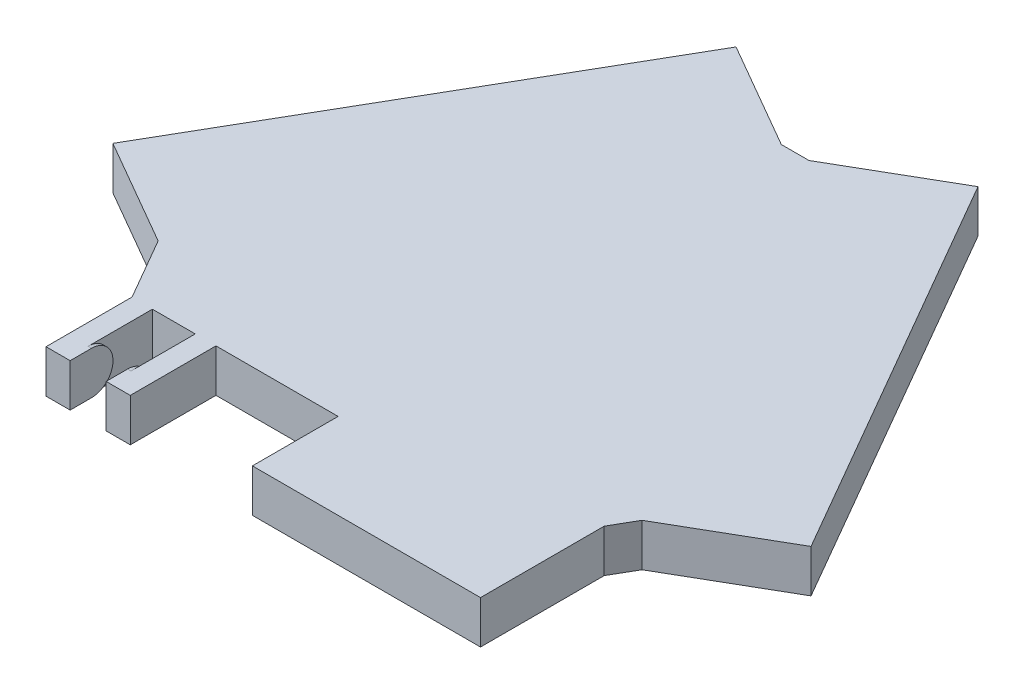
SolidWorks part; units mm, degrees
material "ABS"
ref_plane "Front Plane" through (0, 0, 0) normal (0, 0, 1) x (1, 0, 0)
ref_plane "Top Plane" through (0, 0, 0) normal (0, 1, 0) x (1, 0, 0)
ref_plane "Right Plane" through (0, 0, 0) normal (1, 0, 0) x (0, 0, -1)
sketch "Sketch1" plane through (0, 0, 0) normal (0, 1, 0) x (1, 0, 0)
  line L0 (23.6714, -35) -> (-23.6714, -35) construction
  line L1 (-21.9393, 38) -> (-43.8786, 0)
  line L2 (-33.8786, -17.3205) -> (-31.9393, -20.6795)
  line L3 (-21.9393, -38) -> (21.9393, -38)
  line L4 (-16.9393, 46.6603) -> (-1.9393, 38)
  line L5 (43.8786, 0) -> (21.9393, 38)
  line L6 (1.9393, 38) -> (-1.9393, 38)
  line L7 (-21.9393, -38) -> (-31.9393, -38)
  line L8 (-31.9393, -38) -> (-31.9393, -20.6795)
  line L9 (0, 0) -> (0, -38) construction
  line L10 (21.9393, -38) -> (31.9393, -38)
  line L11 (31.9393, -38) -> (31.9393, -20.6795)
  line L12 (31.9393, -20.6795) -> (33.8786, -17.3205)
  line L13 (21.9393, -38) -> (23.6714, -35) [skipped]
  line L14 (-21.9393, 38) -> (-16.9393, 46.6603)
  line L15 (-43.8786, 0) -> (-48.8786, -8.6603)
  line L16 (-48.8786, -8.6603) -> (-33.8786, -17.3205)
  line L17 (48.8786, -8.6603) -> (33.8786, -17.3205)
  line L18 (43.8786, 0) -> (48.8786, -8.6603)
  line L19 (21.9393, 38) -> (16.9393, 46.6603)
  line L20 (16.9393, 46.6603) -> (1.9393, 38)
  circle A1 centre (0, 0) radius 38 construction
  point P33 (0, 0)
  dimension "D1" = 35
  dimension "D2" = 76
  dimension "D3" = 3
  dimension "D4" = 10
  dimension "D5" = 43.8786
  dimension "D6" = 3
extrude "Boss-Extrude1" add sketch "Sketch1" along normal blind 6 contours L19 L20 L6 L4 L14 L1 L15 L16 L2 L8 L7 L3 L10 L11 L12 L17 L18 L5 region at (0, 0, 0)
sketch "Sketch2" plane through (0, 6, 0) normal (0, 1, 0) x (1, 0, 0)
  line L0 (-20, -40.1141) -> (-20, -26)
  line L1 (-20, -26) -> (-26, -26)
  line L2 (-17.1, -26) -> (0, -26)
  line L3 (-17.1, -40.1141) -> (0, -40.1141)
  line L4 (-20, -40.1141) -> (-17.1, -40.1141) construction
  line L5 (31.9393, -38) -> (-31.9393, -38) construction
  line L12 (-31.9393, -38) -> (-31.9393, -20.6795) construction
  line L13 (0, -26) -> (0, -40.1141)
  line L16 (-26, -26) -> (-26, -40.1141)
  line L17 (-26, -40.1141) -> (-28.9, -40.1141) construction
  line L18 (-17.1, -40.1141) -> (-17.1, -26)
  line L19 (-28.9, -40.1141) -> (-28.9, -25.9437)
  line L20 (-28.9, -25.9437) -> (-31.9393, -20.6795)
  line L21 (-31.9393, -20.6795) -> (-31.9393, -40.1141)
  line L22 (-31.9393, -40.1141) -> (-28.9, -40.1141)
  line L23 (-26, -40.1141) -> (-20, -40.1141)
  line L24 (0, 0) -> (0, -40.1141) construction
  line L25 (-20, -40.1141) -> (-20, -38)
  point P41 (0, 0)
  dimension "D2" = 12
  dimension "D3" = 20
  dimension "D5" = 6
  dimension "D4" = 2.9
extrude "Cut-Extrude1" cut sketch "Sketch2" against normal through all contours L19 L20 | L1 L16 L0 | L18 L13 L2 | L18 L3 L13 | L16 L23 L0 | L21 L22 L19 region at (-23, 6, 33.0571) region at (-8.55, 6, 33.0571) region at (-30.499, 6, 31.6442)
ref_plane "Plane1" through (-23, 0, 0) normal (-1, 0, 0) x (0, 0, 1)
sketch "Sketch16" plane through (-20, 0, 0) normal (-1, 0, 0) x (0, 0, 1)
  line L0 (38, 6) -> (38, 0)
  line L1 (38, 0) -> (35, 0)
  line L2 (38, 0) -> (38, 6) construction
  line L3 (32, 0) -> (32, 6) construction
  line L4 (38, 6) -> (26, 6) construction
  line L5 (35, 6) -> (38, 6)
  line L6 (32, 3) -> (38, 3) construction
  line L7 (35, 6) -> (35, 3) construction
  line L8 (35, 3) -> (35, 0) construction
  line L9 (38, 0) -> (26, 0) construction
  arc A0 (35, 0) -> (35, 6) centre (35, 3) cw
  point P6 (0, 0)
extrude "Boss-Extrude2" add sketch "Sketch16" along normal blind 0.48
mirror "Mirror18" about plane through (-23, 0, 0) normal (-1, 0, 0) of "Boss-Extrude2"
sketch "Sketch3" plane through (-20.48, 0, 0) normal (-1, 0, 0) x (0, 0, 1)
  line L0 (38, 3) -> (26, 3) construction
  line L1 (38, 6) -> (38, 0) construction
  line L2 (26, 0) -> (26, 6) construction
  line L3 (35, 6) -> (35, 0) construction
  line L4 (35, 6) -> (26, 6) construction
  line L5 (35, 0) -> (26, 0) construction
  point P12 (35, 3)
  dimension "D1" = 3
